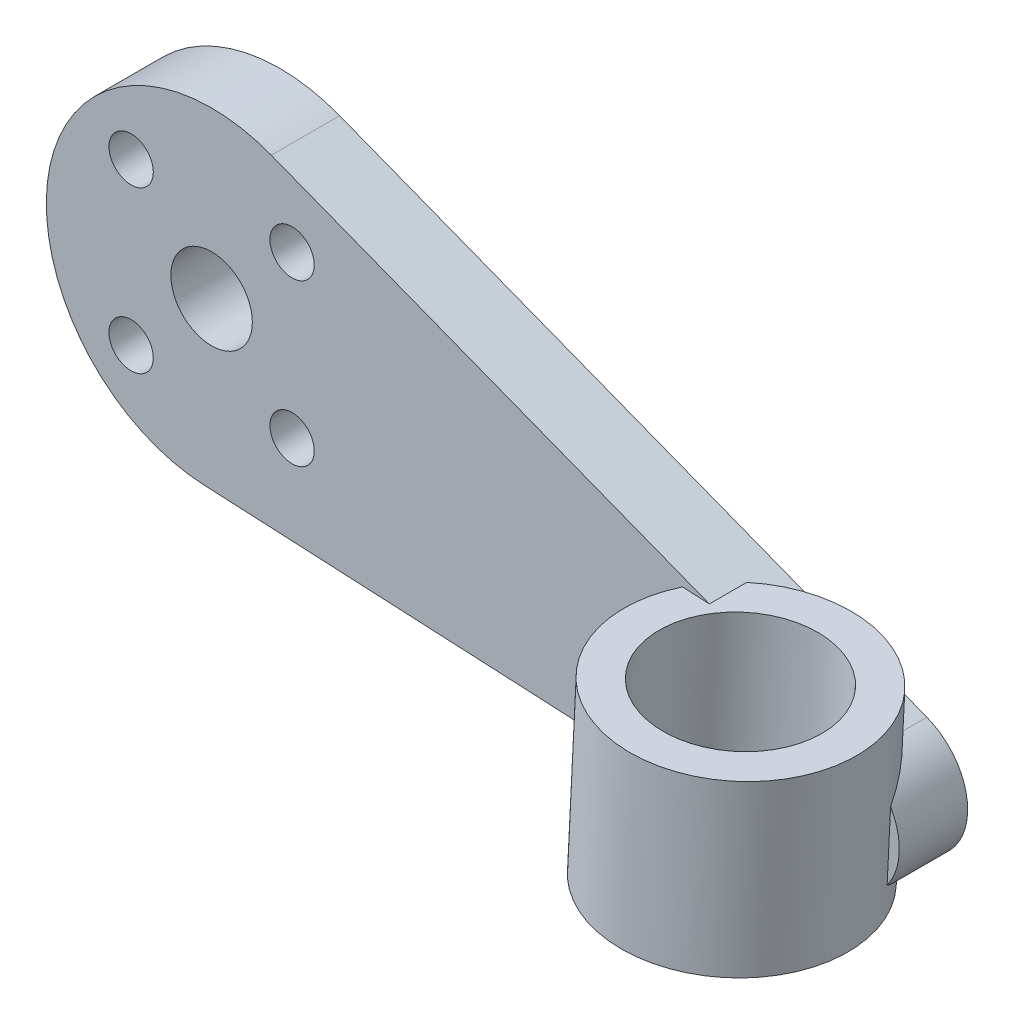
SolidWorks part; units mm, degrees
material "ABS"
ref_plane "Front Plane" through (0, 0, 0) normal (0, 0, 1) x (1, 0, 0)
ref_plane "Top Plane" through (0, 0, 0) normal (0, 1, 0) x (1, 0, 0)
ref_plane "Right Plane" through (0, 0, 0) normal (1, 0, 0) x (0, 0, -1)
ref_plane "Plane1" through (0, 0, 0) normal (0, 0, -1) x (-1, 0, 0)
sketch "Sketch1" plane through (0, 0, 0) normal (0, 0, -1) x (-1, 0, 0)
  line L0 (-54.9006, 0.2614) -> (-46.1167, 9.6815) construction
  line L1 (-54.6285, -5.2121) -> (-0.5934, -2.5259)
  line L3 (-54.9006, 0.2614) -> (-1.2984, 11.6566) construction
  line L4 (-8.3993, 23.9536) -> (-43.781, 5.2606)
  line L5 (-46.7655, 4.7237) -> (-54.1894, 5.6953)
  circle A0 centre (-46.1167, 9.6815) radius 4 construction
  arc A2 (-54.1894, 5.6953) -> (-54.6285, -5.2121) centre (-54.9006, 0.2614) ccw
  arc A3 (-0.5934, -2.5259) -> (-8.3993, 23.9536) centre (-1.2984, 11.6566) ccw
  arc A4 (-46.7655, 4.7237) -> (-43.781, 5.2606) centre (-46.1167, 9.6815) ccw
  dimension "D2" = 14.2
  dimension "D3" = 12.88
  dimension "D5" = 35
  dimension "D6" = 8
  dimension "D7" = 10
  dimension "D1" = 54.8
extrude "Boss-Extrude1" add sketch "Sketch1" against normal blind 15
sketch "Sketch10" plane through (0, 0, 0) normal (0, 0, -1) x (-1, 0, 0)
  circle A0 centre (-1.2984, 11.6566) radius 14.2
  arc A1 (-0.5934, -2.5259) -> (-8.3993, 23.9536) centre (-1.2984, 11.6566) ccw construction
  circle A2 centre (-54.9006, 0.2614) radius 5.4803
  arc A3 (-54.1894, 5.6953) -> (-54.6285, -5.2121) centre (-54.9006, 0.2614) ccw construction
  point P5 (-1.2984, 11.6566)
hole_wizard "CBORE for M6 Hex Head Bolt1" positions "Sketch7" profile "Sketch6" counterbore size "M6" standard "Ansi Metric" end condition through all
sketch "Sketch7" plane through (0, 0, 0) normal (0, 0, -1) x (-1, 0, 0)
  point P0 (-1.2984, 11.6566)
sketch "Sketch6" plane through (1.2984, 11.6566, 0) normal (1, 0, 0) x (0, 1, 0)
  line L0 (0, 0) -> (0, 15)
  line L1 (0, 15) -> (3.5, 15)
  line L3 (3.5, 15) -> (3.5, 3)
  line L4 (3.5, 3) -> (12.8, 3)
  line L5 (12.8, 3) -> (12.8, 0)
  line L7 (12.8, 0) -> (0, 0)
  line L11 (0, -6.35) -> (0, 107.95) construction
  dimension "Thru Hole Dia." = 7
  dimension "Thru Hole Depth" = 15
  dimension "C'Bore Dia." = 25.6
  dimension "C'Bore Depth" = 3
ref_plane "Plane4" through (0, 0, 7.5) normal (0, 0, -1) x (-1, 0, 0)
sketch "Sketch30" plane through (0, 0, 15) normal (0, 0, 1) x (1, 0, 0)
  line L1 (68.7065, -22.2417) -> (-19.1857, -22.2417)
  line L2 (68.7065, -22.2417) -> (68.7065, 41.145)
  line L3 (68.7065, 41.145) -> (-19.1857, 41.145)
  line L4 (-19.1857, -22.2417) -> (-19.1857, 41.145)
extrude "Cut-Extrude8" cut sketch "Sketch30" against normal blind 0.125
sketch "Sketch31" plane through (0, 0, 0) normal (0, 0, -1) x (-1, 0, 0)
  line L1 (-64.611, 30.1264) -> (17.734, 30.1264)
  line L2 (-64.611, 30.1264) -> (-64.611, -8.8981)
  line L3 (-64.611, -8.8981) -> (17.734, -8.8981)
  line L4 (17.734, 30.1264) -> (17.734, -8.8981)
extrude "Cut-Extrude9" cut sketch "Sketch31" against normal blind 0.125
sketch "Sketch38" plane through (0, 0, 14.875) normal (0, 0, 1) x (1, 0, 0)
  circle A0 centre (1.2984, 11.6566) radius 3.5 construction
  circle A1 centre (1.2984, 11.6566) radius 3.5
  circle A2 centre (-5.616, 18.5718) radius 1.905
  circle A3 centre (8.2136, 18.571) radius 1.905
  circle A4 centre (8.2128, 4.7414) radius 1.905
  circle A5 centre (-5.6168, 4.7422) radius 1.905
  line B0 (3.7785, 13.3445) -> (3.7783, 9.9684)
  line B1 (-14.7035, 12.2926) -> (-1.6336, 12.2918)
  line B2 (-14.7033, 16.4201) -> (-14.7035, 12.2926)
  line B3 (-11.9069, 16.4199) -> (-14.7033, 16.4201)
  line B4 (-11.2749, 6.8948) -> (-11.2749, 6.8267)
  line B5 (-14.7039, 6.8951) -> (-11.2749, 6.8948)
  line B6 (-14.7036, 11.0226) -> (-14.7039, 6.8951)
  line B7 (-1.6336, 11.0218) -> (-14.7036, 11.0226)
  arc B8 (2.6475, 8.977) -> (3.7783, 9.9684) centre (2.7783, 9.9684) ccw
  arc B9 (3.7785, 13.3445) -> (2.6478, 14.336) centre (2.7785, 13.3446) ccw
  arc B10 (2.6478, 14.336) -> (-1.6336, 12.2918) centre (1.2984, 11.6566) ccw
  arc B11 (-11.9069, 16.4199) -> (-8.9599, 19.0076) centre (-11.9068, 19.3917) ccw
  arc B12 (-4.0299, 21.5478) -> (-8.9599, 19.0076) centre (-5.616, 18.5718) ccw
  arc B13 (-4.0299, 21.5478) -> (-1.7731, 21.3412) centre (-2.6561, 24.1255) ccw
  arc B14 (4.3711, 21.3408) -> (-1.7731, 21.3412) centre (1.2984, 11.6566) ccw
  arc B15 (4.3711, 21.3408) -> (6.628, 21.5471) centre (5.2545, 24.1251) ccw
  arc B16 (11.1896, 16.985) -> (6.628, 21.5471) centre (8.2136, 18.571) ccw
  arc B17 (11.1896, 16.985) -> (10.983, 14.7281) centre (13.7674, 15.6111) ccw
  arc B18 (10.9827, 8.5839) -> (10.983, 14.7281) centre (1.2984, 11.6566) ccw
  arc B19 (10.9827, 8.5839) -> (11.189, 6.3271) centre (13.7669, 7.7006) ccw
  arc B20 (6.6268, 1.7654) -> (11.189, 6.3271) centre (8.2128, 4.7414) ccw
  arc B21 (6.6268, 1.7654) -> (4.3699, 1.972) centre (5.253, -0.8123) ccw
  arc B22 (-1.7742, 1.9724) -> (4.3699, 1.972) centre (1.2984, 11.6566) ccw
  arc B23 (-1.7742, 1.9724) -> (-4.0311, 1.7661) centre (-2.6576, -0.8119) ccw
  arc B24 (-8.9608, 4.3068) -> (-4.0311, 1.7661) centre (-5.6168, 4.7422) ccw
  arc B25 (-8.9608, 4.3068) -> (-11.2749, 6.8267) centre (-11.9077, 3.9231) ccw
  arc B26 (-1.6336, 11.0218) -> (2.6475, 8.977) centre (1.2984, 11.6566) ccw
  dimension "D1" = 3.81
sketch_block_instance "Block1-1"
sketch_block "Block1"
extrude "Cut-Extrude10" cut sketch "Sketch38" against normal through all contours A2 | A3 | A4 | A5
sketch "Sketch39" plane through (0, 0, 0.125) normal (0, 0, -1) x (-1, 0, 0)
  circle A1 centre (-1.2984, 11.6566) radius 12.8 construction
  circle A2 centre (-1.2984, 11.6566) radius 12.8
extrude "Cut-Extrude11" cut sketch "Sketch39" against normal offset from surface (7.75 mm away) 7 flip side to cut contours A2 up to face at (-3.7118, 4.7422, 14.875)
sketch "Sketch40" plane through (0, 0, 14.875) normal (0, 0, 1) x (1, 0, 0)
  circle A0 centre (1.2984, 11.6566) radius 13
  dimension "D1" = 26
extrude "Cut-Extrude12" cut sketch "Sketch40" against normal offset from surface (6 mm away) 1 up to face at (32.9108, 6.1436, 7.875)
sketch "Sketch42" plane through (0, 0, 14.875) normal (0, 0, 1) x (1, 0, 0)
  line L0 (6.4237, 24.8994) -> (56.8786, 5.3722)
  line L3 (43.781, 5.2606) -> (8.3993, 23.9536)
  line L4 (0.5934, -2.5259) -> (54.6285, -5.2121)
  line L5 (54.1894, 5.6953) -> (46.7655, 4.7237)
  line L6 (43.781, 5.2606) -> (8.3993, 23.9536)
  line L8 (54.1894, 5.6953) -> (46.7655, 4.7237)
  arc A0 (54.6285, -5.2121) -> (54.1894, 5.6953) centre (54.9006, 0.2614) ccw construction
  arc A3 (8.3993, 23.9536) -> (0.5934, -2.5259) centre (1.2984, 11.6566) ccw
  arc A4 (54.6285, -5.2121) -> (54.1894, 5.6953) centre (54.9006, 0.2614) ccw
  arc A5 (43.781, 5.2606) -> (46.7655, 4.7237) centre (46.1167, 9.6815) ccw
  arc A6 (8.3993, 23.9536) -> (6.4237, 24.8994) centre (1.2984, 11.6566) ccw
  arc A7 (56.8786, 5.3722) -> (54.1894, 5.6953) centre (54.9006, 0.2614) ccw
  arc A8 (43.781, 5.2606) -> (46.7655, 4.7237) centre (46.1167, 9.6815) ccw
  dimension "D1" = 0
extrude "Boss-Extrude2" add sketch "Sketch42" against normal up to surface (7 mm away) up to face at (32.9108, 6.1436, 7.875)
sketch "Sketch43" plane through (0, 0, 7.875) normal (0, 0, -1) x (-1, 0, 0)
  line L2 (-6.4237, 24.8994) -> (-56.8786, 5.3722)
  line L3 (-54.6285, -5.2121) -> (-0.5934, -2.5259)
  line L4 (-6.4237, 24.8994) -> (-56.8786, 5.3722)
  line L5 (-54.6285, -5.2121) -> (-0.5934, -2.5259)
  circle A0 centre (-1.2984, 11.6566) radius 12.8 construction
  circle A1 centre (-1.2984, 11.6566) radius 12.8
  arc A2 (-0.5934, -2.5259) -> (-6.4237, 24.8994) centre (-1.2984, 11.6566) ccw
  arc A3 (-56.8786, 5.3722) -> (-54.6285, -5.2121) centre (-54.9006, 0.2614) ccw
  arc A4 (-0.5934, -2.5259) -> (-6.4237, 24.8994) centre (-1.2984, 11.6566) ccw
  arc A5 (-56.8786, 5.3722) -> (-54.6285, -5.2121) centre (-54.9006, 0.2614) ccw
  dimension "D1" = 0
extrude "Boss-Extrude4" add sketch "Sketch43" along normal up to surface (4.875 mm away) up to face at (-3.7118, 4.7422, 3)
sketch "Sketch45" plane through (0, 0, 14.875) normal (0, 0, 1) x (1, 0, 0)
  line L2 (56.8786, 5.3722) -> (6.4237, 24.8994)
  line L3 (0.5934, -2.5259) -> (54.6285, -5.2121)
  line L4 (56.8786, 5.3722) -> (6.4237, 24.8994)
  line L5 (0.5934, -2.5259) -> (54.6285, -5.2121)
  circle A0 centre (1.2984, 11.6566) radius 13 construction
  circle A1 centre (1.2984, 11.6566) radius 13
  arc A2 (54.6285, -5.2121) -> (56.8786, 5.3722) centre (54.9006, 0.2614) ccw
  arc A3 (6.4237, 24.8994) -> (0.5934, -2.5259) centre (1.2984, 11.6566) ccw
  arc A4 (54.6285, -5.2121) -> (56.8786, 5.3722) centre (54.9006, 0.2614) ccw
  arc A5 (6.4237, 24.8994) -> (0.5934, -2.5259) centre (1.2984, 11.6566) ccw
  dimension "D1" = 0
extrude "Cut-Extrude13" cut sketch "Sketch45" against normal up to surface (6 mm away) contours L4 A5 L5 A4 up to face at (14.2984, 11.6566, 8.875)
sketch "Sketch46" plane through (-0.1238, -2.4902, 0) normal (-0.0497, -0.9988, 0) x (0.9988, -0.0497, 0)
  line L0 (0.7181, 3) -> (54.8199, 3) construction
  line L1 (60.3001, 3) -> (60.3001, 8.875) construction
  circle A0 centre (50.3001, 13) radius 10
  dimension "D1" = 20
extrude "Boss-Extrude5" add sketch "Sketch46" against normal blind 15
sketch "Sketch47" plane through (-0.1238, -2.4902, 0) normal (-0.0497, -0.9988, 0) x (0.9988, -0.0497, 0)
  circle A0 centre (50.3001, 13) radius 7
  arc A1 (54.8199, 4.0797) -> (41.1906, 8.875) centre (50.3001, 13) ccw construction
  dimension "D1" = 14
extrude "Cut-Extrude14" cut sketch "Sketch47" against normal through all
